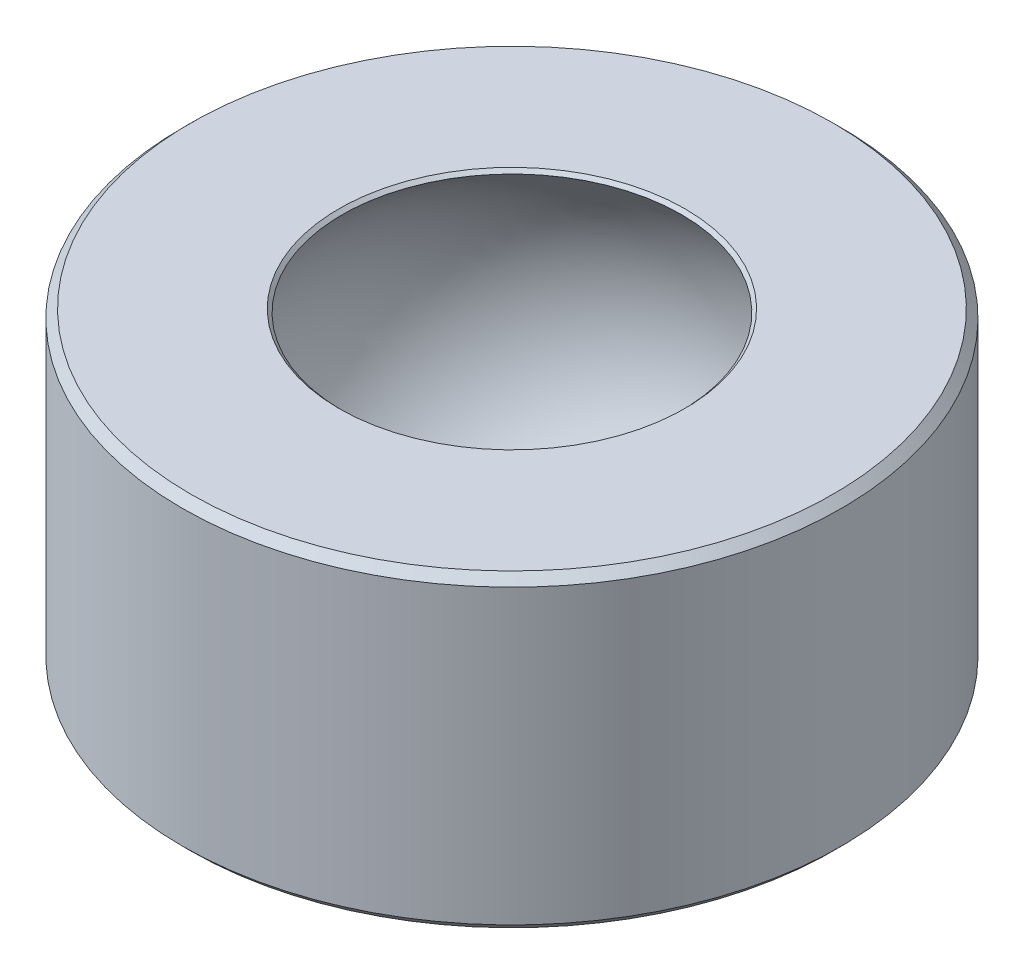
SolidWorks part; units mm, degrees
ref_plane "Front Plane" through (0, 0, 0) normal (0, 0, 1) x (1, 0, 0)
ref_plane "Top Plane" through (0, 0, 0) normal (0, 1, 0) x (1, 0, 0)
ref_plane "Right Plane" through (0, 0, 0) normal (1, 0, 0) x (0, 0, -1)
sketch "Sketch1" plane through (0, 0, 0) normal (0, 1, 0) x (1, 0, 0)
  circle A0 centre (0, 0) radius 2
  circle A1 centre (0, 0) radius 3 construction
  circle A2 centre (0, 0) radius 4
  dimension "D1" = 8
  dimension "D2" = 6
  dimension "D3" = 4
extrude "Boss-Extrude1" add sketch "Sketch1" along normal blind 1.875 and the other way blind 1.875
sketch "Sketch2" plane through (0, 0, 0) normal (0, 1, 0) x (1, 0, 0)
  line L0 (0, 3) -> (0, -3)
  circle A0 centre (0, 0) radius 3 construction
  arc A1 (0, 3) -> (0, -3) centre (0, 0) ccw
sketch "Sketch3" plane through (0, 0, 0) normal (1, 0, 0) x (0, 0, -1)
  line L0 (-2, 1.875) -> (-2, -1.875)
  line L1 (0, 0) -> (0, -3.1307) construction
  arc A0 (-2, 1.875) -> (-2, -1.875) centre (-0.7422, 0) ccw
revolve "Cut-Revolve1" cut sketch "Sketch3" angle 360 about L1
chamfer "Chamfer1" distance 0.1 angle 45 4 edges at (0, 1.875, 4) (0, -1.875, 4) (0, 1.875, 2) (0, -1.875, 2)
